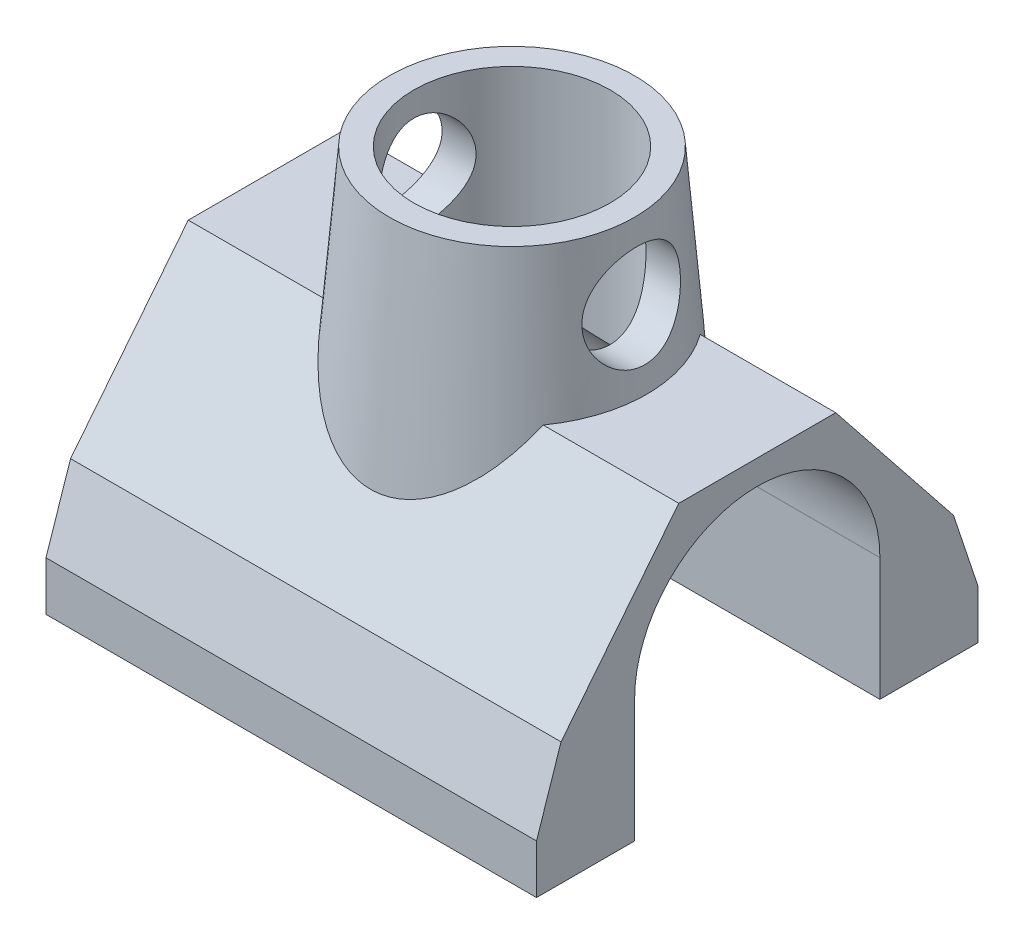
SolidWorks part; units mm, degrees
ref_plane "Спереди" through (0, 0, 0) normal (0, 0, 1) x (1, 0, 0)
ref_plane "Сверху" through (0, 0, 0) normal (0, 1, 0) x (1, 0, 0)
ref_plane "Справа" through (0, 0, 0) normal (1, 0, 0) x (0, 0, -1)
sketch "Эскиз1" plane through (0, 0, 0) normal (1, 0, 0) x (0, 0, -1)
  line L0 (-45, 9.8864) -> (-45, -0.1136)
  line L1 (-45, -0.1136) -> (-25, -0.1136)
  line L2 (-25, -0.1136) -> (-25, 24.8864)
  line L4 (-40, 24.8864) -> (-45, 9.8864)
  line L5 (0, 0) -> (-64.5475, -0.2932) construction
  line L6 (0, 0) -> (0, 24.8864) construction
  line L8 (25, -0.1136) -> (25, 24.8864)
  line L9 (45, -0.1136) -> (25, -0.1136)
  line L10 (45, 9.8864) -> (45, -0.1136)
  line L11 (40, 24.8864) -> (45, 9.8864)
  line L12 (-16, 55) -> (16, 55)
  line L13 (-40, 24.8864) -> (-16, 55)
  line L14 (16, 55) -> (40, 24.8864)
  arc A0 (25, 24.8864) -> (-25, 24.8864) centre (0, 24.8864) ccw
  point P16 (-16.5148, 55)
  dimension "D1" = 50
  dimension "D2" = 40
  dimension "D3" = 45
  dimension "D4" = 10
  dimension "D6" = 55
  dimension "D7" = 32
  dimension "D8" = 16
extrude "Бобышка-Вытянуть1" add sketch "Эскиз1" along normal blind 50 and the other way blind 50
ref_plane "Плоскость4" through (0, 25, 0) normal (0, 1, 0) x (1, 0, 0)
sketch "Эскиз3" plane through (0, 25, 0) normal (0, 1, 0) x (1, 0, 0)
  circle A0 centre (0, 0) radius 30
  dimension "D1" = 60
ref_plane "Плоскость5" through (0, 85, 0) normal (0, 1, 0) x (1, 0, 0)
sketch "Эскиз5" plane through (0, 85, 0) normal (0, 1, 0) x (1, 0, 0)
  circle A0 centre (0, 0) radius 25
  dimension "D1" = 50
loft "По сечениям1" add profiles "Эскиз3", "Эскиз5" connector at (-24.7806, 25, 16.9092) connector at (-20.4447, 85, 14.388)
sketch "Эскиз6" plane through (-50, 0, 0) normal (-1, 0, 0) x (0, 0, 1)
  line L0 (15.1986, 25) -> (-15.1986, 25) construction
  line L1 (0, -46.8125) -> (0, 46.8125) construction
  line L2 (15.1986, 85) -> (-15.1986, 85) construction
  circle A0 centre (0, 25) radius 25
  circle A1 centre (0, 70) radius 10
  dimension "D1" = 50
  dimension "D2" = 20
  dimension "D3" = 15
extrude "Вырез-Вытянуть1" cut sketch "Эскиз6" against normal blind 100 contours A1 | A0
sketch "Эскиз7" plane through (0, 85, 0) normal (0, 1, 0) x (1, 0, 0)
  circle A0 centre (0, 0) radius 20
  dimension "D1" = 40
extrude "Вырез-Вытянуть2" cut sketch "Эскиз7" against normal blind 100
